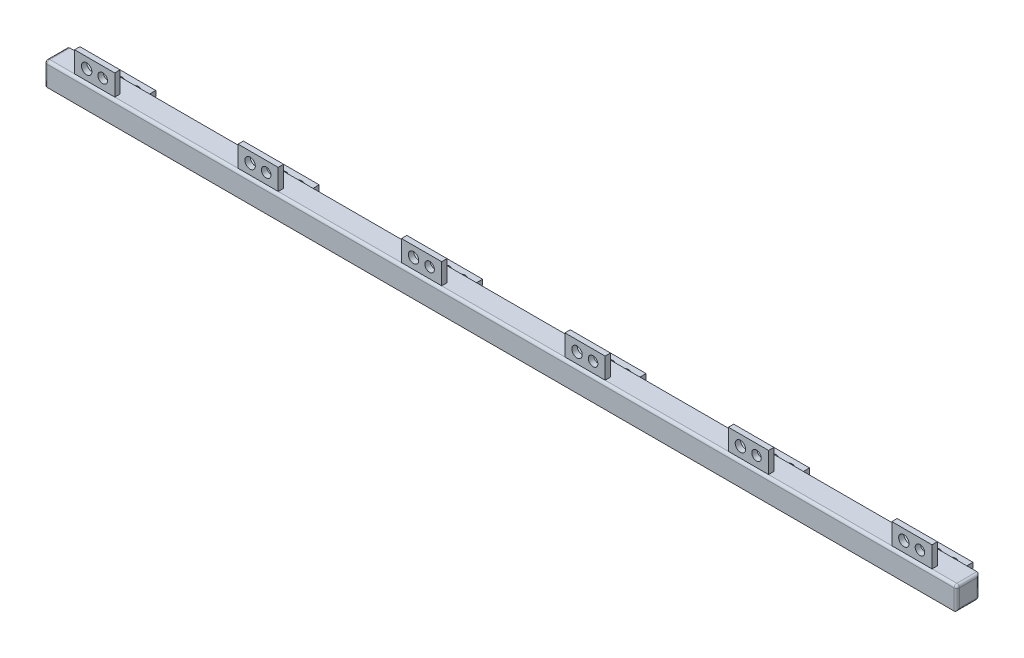
SolidWorks part; units mm, degrees
ref_plane "Front Plane" through (0, 0, 0) normal (0, 0, 1) x (1, 0, 0)
ref_plane "Top Plane" through (0, 0, 0) normal (0, 1, 0) x (1, 0, 0)
ref_plane "Right Plane" through (0, 0, 0) normal (1, 0, 0) x (0, 0, -1)
sketch "Sketch1" plane through (0, 0, 0) normal (1, 0, 0) x (0, 0, -1)
  line L1 (0, 0) -> (8.5, 0)
  line L2 (0, 0) -> (0, 8.5)
  line L3 (0, 8.5) -> (8.5, 8.5)
  line L4 (8.5, 0) -> (8.5, 8.5)
  dimension "D1" = 8.5
  dimension "D2" = 8.5
extrude "Boss-Extrude1" add sketch "Sketch1" along normal blind 340.5
sketch "Sketch2" plane through (0, 8.5, 0) normal (0, 1, 0) x (1, 0, 0)
  line L0 (340.5, 8.5) -> (0, 8.5) construction
  line L1 (6.75, 8.5) -> (333.75, 8.5) construction
  line L2 (6.75, 8.5) -> (6.75, 0) construction
  line L3 (6.75, 0) -> (333.75, 0) construction
  line L4 (333.75, 8.5) -> (333.75, 0) construction
  line L5 (340.5, 0) -> (0, 0) construction
  line L6 (340.5, 8.5) -> (340.5, 0) construction
  line L9 (0, 8.5) -> (0, 0) construction
  line L10 (17.75, 1) -> (17.75, 3) construction
  line L11 (10.25, 3) -> (25.25, 3)
  line L12 (10.25, 3) -> (10.25, 1)
  line L13 (10.25, 1) -> (25.25, 1)
  line L14 (25.25, 3) -> (25.25, 1)
  line L15 (71.25, 1) -> (86.25, 1)
  line L16 (71.25, 3) -> (71.25, 1)
  line L17 (71.25, 3) -> (86.25, 3)
  line L18 (86.25, 3) -> (86.25, 1)
  line L19 (132.25, 1) -> (147.25, 1)
  line L20 (132.25, 3) -> (132.25, 1)
  line L21 (132.25, 3) -> (147.25, 3)
  line L22 (147.25, 3) -> (147.25, 1)
  line L23 (193.25, 1) -> (208.25, 1)
  line L24 (193.25, 3) -> (193.25, 1)
  line L25 (193.25, 3) -> (208.25, 3)
  line L26 (208.25, 3) -> (208.25, 1)
  line L27 (254.25, 1) -> (269.25, 1)
  line L28 (254.25, 3) -> (254.25, 1)
  line L29 (254.25, 3) -> (269.25, 3)
  line L30 (269.25, 3) -> (269.25, 1)
  line L31 (315.25, 1) -> (330.25, 1)
  line L32 (315.25, 3) -> (315.25, 1)
  line L33 (315.25, 3) -> (330.25, 3)
  line L34 (330.25, 3) -> (330.25, 1)
  point P8 (340.5, 4.25)
  dimension "D1" = 327
  dimension "D2" = 6.75
  dimension "D3" = 6.75
  dimension "D4" = 2
  dimension "D5" = 15
  dimension "D6" = 11
  dimension "D8" = 7.5
  dimension "D7" = 6
extrude "Boss-Extrude2" add sketch "Sketch2" along normal blind 7.8
sketch "Sketch3" plane through (0, 0, -1) normal (0, 0, 1) x (1, 0, 0)
  line L0 (10.25, 8.5) -> (25.25, 8.5) construction
  line L3 (10.25, 16.3) -> (10.25, 8.5) construction
  circle A0 centre (14.75, 12.4) radius 1.9455
  circle A1 centre (20.75, 12.4) radius 1.7775
  circle A2 centre (75.75, 12.4) radius 1.9455
  circle A3 centre (81.75, 12.4) radius 1.7775
  circle A4 centre (136.75, 12.4) radius 1.9455
  circle A5 centre (142.75, 12.4) radius 1.7775
  circle A6 centre (197.75, 12.4) radius 1.9455
  circle A7 centre (203.75, 12.4) radius 1.7775
  circle A8 centre (258.75, 12.4) radius 1.9455
  circle A9 centre (264.75, 12.4) radius 1.7775
  circle A10 centre (319.75, 12.4) radius 1.9455
  circle A11 centre (325.75, 12.4) radius 1.7775
  dimension "D1" = 3.9
  dimension "D2" = 3.9
  dimension "D3" = 6
  dimension "D4" = 4.5
  dimension "D5" = 6
extrude "Cut-Extrude1" cut sketch "Sketch3" against normal blind 7.8
sketch "Sketch4" plane through (0, 0, -8.5) normal (0, 0, -1) x (-1, 0, 0)
  line L0 (-269.25, 1) -> (-254.25, 1)
  line L1 (-330.25, 3) -> (-315.25, 3)
  line L2 (-330.25, 3) -> (-330.25, 1)
  line L3 (-330.25, 1) -> (-315.25, 1)
  line L4 (-315.25, 3) -> (-315.25, 1)
  line L5 (-269.25, 3) -> (-269.25, 1)
  line L6 (-269.25, 3) -> (-254.25, 3)
  line L7 (-254.25, 3) -> (-254.25, 1)
  line L8 (-208.25, 1) -> (-193.25, 1)
  line L9 (-208.25, 3) -> (-208.25, 1)
  line L10 (-208.25, 3) -> (-193.25, 3)
  line L11 (-193.25, 3) -> (-193.25, 1)
  line L12 (-147.25, 1) -> (-132.25, 1)
  line L13 (-147.25, 3) -> (-147.25, 1)
  line L14 (-147.25, 3) -> (-132.25, 3)
  line L15 (-132.25, 3) -> (-132.25, 1)
  line L16 (-86.25, 1) -> (-71.25, 1)
  line L17 (-86.25, 3) -> (-86.25, 1)
  line L18 (-86.25, 3) -> (-71.25, 3)
  line L19 (-71.25, 3) -> (-71.25, 1)
  line L20 (-25.25, 1) -> (-10.25, 1)
  line L21 (-25.25, 3) -> (-25.25, 1)
  line L22 (-25.25, 3) -> (-10.25, 3)
  line L23 (-10.25, 3) -> (-10.25, 1)
  line L24 (-340.5, 8.5) -> (0, 8.5) construction
  dimension "D1" = 2
  dimension "D2" = 15
  dimension "D4" = 5.5
  dimension "D3" = 6
extrude "Boss-Extrude3" add sketch "Sketch4" along normal blind 7.8
sketch "Sketch5" plane through (0, 1, 0) normal (0, -1, 0) x (1, 0, 0)
  line L0 (330.25, -16.3) -> (330.25, -8.5) construction
  line L2 (330.25, -8.5) -> (315.25, -8.5) construction
  circle A0 centre (325.75, -12.4) radius 1.95
  circle A1 centre (319.75, -12.4) radius 1.95
  circle A2 centre (264.75, -12.4) radius 1.95
  circle A3 centre (258.75, -12.4) radius 1.95
  circle A4 centre (203.75, -12.4) radius 1.95
  circle A5 centre (197.75, -12.4) radius 1.95
  circle A6 centre (142.75, -12.4) radius 1.95
  circle A7 centre (136.75, -12.4) radius 1.95
  circle A8 centre (81.75, -12.4) radius 1.95
  circle A9 centre (75.75, -12.4) radius 1.95
  circle A10 centre (20.75, -12.4) radius 1.95
  circle A11 centre (14.75, -12.4) radius 1.95
  dimension "D1" = 3.9
  dimension "D2" = 3.9
  dimension "D3" = 6
  dimension "D4" = 4.5
  dimension "D6" = 3.9
  dimension "D5" = 6
extrude "Cut-Extrude2" cut sketch "Sketch5" against normal blind 7.8 contours A2 | A3 | A4 | A5 | A6 | A7 | A10 | A11 | A8 | A9 | A0 | A1 region at (264.75, 1, -12.4) region at (258.75, 1, -12.4) region at (203.75, 1, -12.4) region at (197.75, 1, -12.4) region at (142.75, 1, -12.4) region at (136.75, 1, -12.4) region at (81.75, 1, -12.4) region at (75.75, 1, -12.4) region at (20.75, 1, -12.4) region at (14.75, 1, -12.4)
fillet "Fillet1" radius 1 2 edges at (340.5, 0, -4.25) (340.5, 4.25, 0)
fillet "Fillet2" radius 1 6 edges at (169.75, 8.5, 0) (340.2071, 8.5, -0.2929) (169.75, 0, -8.5) (340.2071, 0.2929, -8.5) (340.5, 8.5, -4.75) (340.5, 4.75, -8.5)
fillet "Fillet3" radius 1 6 edges at (0, 0.2929, -8.2071) (0, 8.2071, -0.2929) (0, 3.75, 0) (0, 0, -3.75) (0, 4.75, -8.5) (0, 8.5, -4.75)
